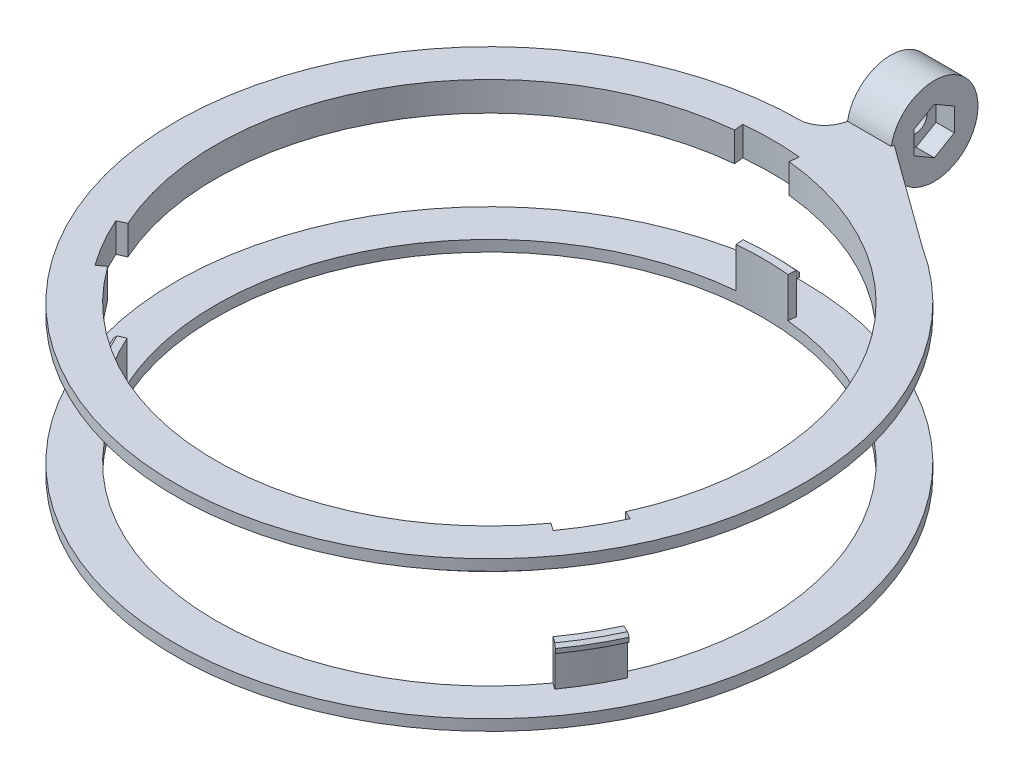
SolidWorks part; units mm, degrees
note: The reader was unsure of these and kept them because the rebuilt part matched: shared geometry of "Esboço120<3>", "Esboço120<4>", "Esboço122<12>", "Esboço123<3>".
ref_plane "Plano frontal" through (0, 0, 0) normal (0, 0, 1) x (1, 0, 0)
ref_plane "Plano superior" through (0, 0, 0) normal (0, 1, 0) x (1, 0, 0)
ref_plane "Plano direito" through (0, 0, 0) normal (1, 0, 0) x (0, 0, -1)
ref_plane "Plano24" through (10, 0, 0) normal (1, 0, 0) x (0, 0, -1)
sketch "Esboço120" plane through (10, 0, 0) normal (1, 0, 0) x (0, 0, -1)
  line L6 (-78.5, 184.9522) -> (-73.5, 176.2919)
  line L7 (-78.5, 176.2919) -> (-73.5, 184.9522)
  line L8 (-80.3301, 178.1221) -> (-71.6699, 183.1221)
  line L9 (-81, 180.6221) -> (-71, 180.6221)
  line L10 (-71.6699, 178.1221) -> (-80.3301, 183.1221)
  line L11 (-76, 185.6221) -> (-76, 175.6221)
  circle A0 centre (-76, 180.6221) radius 6
  circle A2 centre (-76, 180.6221) radius 1.5
  circle A4 centre (-76, 180.6221) radius 5
  dimension "D3" = 1
extrude "Ressalto-extrusão39" add sketch "Esboço120" along normal blind 6 separate body contours A0
extrude "Corte-Extrusão-Fina1" cut sketch "Esboço120<3>" along normal blind 0.4 thin contours L9 | L10 | L6 | L11 | L7 | L8
sketch "Esboço120<3>" plane through (10, 0, 0) normal (1, 0, 0) x (0, 0, -1) same geometry as "Esboço120"
extrude "Corte-extrusão49" cut sketch "Esboço120<4>" along normal up to next contours A2
sketch "Esboço120<4>" plane through (10, 0, 0) normal (1, 0, 0) x (0, 0, -1) same geometry as "Esboço120"
sketch "Esboço121" plane through (16, 0, 0) normal (1, 0, 0) x (0, 0, -1)
  line L1 (-76, 183.7975) -> (-78.75, 182.2098)
  line L2 (-78.75, 182.2098) -> (-78.75, 179.0343)
  line L3 (-78.75, 179.0343) -> (-76, 177.4466)
  line L4 (-76, 177.4466) -> (-73.25, 179.0343)
  line L5 (-73.25, 179.0343) -> (-73.25, 182.2098)
  line L6 (-73.25, 182.2098) -> (-76, 183.7975)
  circle A0 centre (-76, 180.6221) radius 2.75 construction
  dimension "D1" = 5.5
extrude "Corte-extrusão50" cut sketch "Esboço121" against normal blind 2.5 contours L1 L2 L3 L4 L5 L6
ref_plane "Plao25" through (0, 180.2338, 0) normal (0, 1, 0) x (1, 0, 0)
sketch "Esboço122" plane through (0, 180.2338, 0) normal (0, 1, 0) x (1, 0, 0)
  line L0 (10, -82) -> (10, -81.5)
  line L1 (10, -82) -> (7, -82) construction
  line L2 (7, -82) -> (7, -85) construction
  line L3 (10, -81.5) -> (16, -81.5)
  line L4 (10.8078, -90.6938) -> (10.9347, -89.4503)
  line L5 (7, -85) -> (7, -93) construction
  line L6 (3.311, -90.6819) -> (3.1881, -89.4379)
  line L7 (41.1629, -143.4643) -> (42.3017, -143.9798)
  line L8 (37.4042, -149.9507) -> (38.4177, -150.6824)
  line L9 (-23.474, -149.8538) -> (-24.4898, -150.5823)
  line L10 (-27.212, -143.3555) -> (-28.3524, -143.8673)
  circle A0 centre (7, -128) radius 43
  circle A1 centre (7, -128) radius 39.5
  circle A2 centre (7, -128) radius 40 construction
  circle A3 centre (7, -128) radius 42 construction
  circle A4 centre (7, -128) radius 37.5
  arc A5 (10.9347, -89.4503) -> (3.1881, -89.4379) centre (7, -128) ccw
  arc A6 (38.4177, -150.6824) -> (42.3017, -143.9798) centre (7, -128) ccw
  arc A7 (-28.3524, -143.8673) -> (-24.4898, -150.5823) centre (7, -128) ccw
  spline S0 degree 2 poles (10, -82) (9.3918, -84.3997) (7, -85) knots 0 0 0 1 1 1
  spline S1 degree 1 poles (16, -81.5) (30.0958, -91.729) knots 0 0 1 1
  point P3 (10, -82)
  point P25 (0, 0)
  point P26 (19.4375, -84.1454)
  point P35 (7, -128)
  point P36 (0, 0)
  point P37 (0, 0)
  point P38 (0, 0)
  dimension "D2" = 3
  dimension "D3" = 86
  dimension "D5" = 79
  dimension "D8" = 80
  dimension "D11" = 1.25
  dimension "D12" = 3
  dimension "D1" = 3
  dimension "D7" = 0.5
  dimension "D4" = 3.5
  dimension "D6" = 0.5
  dimension "D9" = 2
  dimension "D10" = 2
extrude "Ressalto-extrusão40" add sketch "Esboço122" along normal blind 1.5 contours S1 L3 L0 S0 A0 | A0 A1 | A1 A4
extrude "Ressalto-extrusão41" add sketch "Esboço122<12>" against normal blind 2.5 contours A1 A4
sketch "Esboço122<12>" plane through (0, 180.2338, 0) normal (0, 1, 0) x (1, 0, 0) same geometry as "Esboço122"
ref_plane "Plano25" through (0, 162.7338, 0) normal (0, -1, 0) x (-1, 0, 0)
sketch "Esboço123" plane through (0, 162.7338, 0) normal (0, -1, 0) x (-1, 0, 0)
  line L0 (-10.6087, -90.674) -> (-10.7154, -89.6295)
  line L1 (-3.5101, -90.6627) -> (-3.4068, -89.6178)
  line L2 (-10.6088, -90.6735) -> (-10.7154, -89.6295) construction
  line L3 (-3.5101, -90.6622) -> (-3.4068, -89.6178) construction
  line L4 (-10.8078, -90.6938) -> (-10.9347, -89.4503) construction
  line L5 (-3.311, -90.6819) -> (-3.1881, -89.4379) construction
  line L6 (27.1296, -143.5377) -> (28.0875, -143.9677)
  line L7 (23.5901, -149.691) -> (24.4434, -150.3029)
  line L8 (27.212, -143.3555) -> (28.3524, -143.8673) construction
  line L9 (23.474, -149.8538) -> (24.4898, -150.5823) construction
  line L10 (-37.5209, -149.7882) -> (-38.3722, -150.4029)
  line L11 (-41.08, -143.6463) -> (-42.0365, -144.0793)
  line L12 (-10.8078, -90.6938) -> (-10.9347, -89.4503) construction
  line L13 (-3.311, -90.6819) -> (-3.1881, -89.4379) construction
  line L14 (-37.4042, -149.9507) -> (-38.4177, -150.6824) construction
  line L15 (-41.1629, -143.4643) -> (-42.3017, -143.9798) construction
  arc A0 (24.4434, -150.3029) -> (28.0875, -143.9677) centre (-7, -128) ccw
  arc A1 (-3.4068, -89.6178) -> (-10.7154, -89.6295) centre (-7, -128) ccw
  arc A2 (24.4898, -150.5823) -> (28.3524, -143.8673) centre (-7, -128) ccw construction
  circle A3 centre (-7, -128) radius 43
  circle A4 centre (-7, -128) radius 43
  circle A5 centre (-7, -128) radius 37.5
  circle A6 centre (-7, -128) radius 37.5
  arc A7 (-3.1881, -89.4379) -> (-10.9347, -89.4503) centre (-7, -128) ccw construction
  arc A8 (-42.0365, -144.0793) -> (-38.3722, -150.4029) centre (-7, -128) ccw
  arc A9 (-42.3017, -143.9798) -> (-38.4177, -150.6824) centre (-7, -128) ccw construction
  arc A10 (-3.1881, -89.4379) -> (-10.9347, -89.4503) centre (-7, -128) ccw construction
  point P35 (-7, -128)
  dimension "D1" = 0.2
  dimension "D2" = 0
  dimension "D3" = 0
  dimension "D4" = 3
extrude "Ressalto-extrusão42" add sketch "Esboço123" along normal blind 1.5 separate body
extrude "Ressalto-extrusão43" add sketch "Esboço123<3>" against normal blind 5.5 contours L11 A8 L10 A6 | A6 L7 A0 L6 | A6 L1 A1 L0
sketch "Esboço123<3>" plane through (0, 162.7338, 0) normal (0, -1, 0) x (-1, 0, 0) same geometry as "Esboço123"
ref_plane "Plano26" through (0, 168.2338, 0) normal (0, 1, 0) x (1, 0, 0)
sketch "Esboço124" plane through (0, 168.2338, 0) normal (0, 1, 0) x (1, 0, 0)
  line L0 (38.3722, -150.4029) -> (38.6977, -150.6353)
  line L1 (42.0365, -144.0793) -> (42.4001, -144.2462)
  line L2 (10.7154, -89.6295) -> (10.7539, -89.2313)
  line L3 (3.4068, -89.6178) -> (3.3695, -89.2196)
  line L4 (-28.0875, -143.9677) -> (-28.4516, -144.1334)
  line L5 (-24.4434, -150.3029) -> (-24.7696, -150.5343)
  arc A0 (38.3722, -150.4029) -> (42.0365, -144.0793) centre (7, -128) ccw construction
  arc A1 (10.7154, -89.6295) -> (3.4068, -89.6178) centre (7, -128) ccw construction
  arc A2 (-28.0875, -143.9677) -> (-24.4434, -150.3029) centre (7, -128) ccw construction
  arc A3 (38.3722, -150.4029) -> (42.0365, -144.0793) centre (7, -128) ccw
  arc A4 (10.7154, -89.6295) -> (3.4068, -89.6178) centre (7, -128) ccw
  arc A5 (-28.0875, -143.9677) -> (-24.4434, -150.3029) centre (7, -128) ccw
  arc A6 (38.6977, -150.6353) -> (42.4001, -144.2462) centre (7, -128) ccw
  arc A7 (10.7539, -89.2313) -> (3.3695, -89.2196) centre (7, -128) ccw
  arc A8 (-28.4516, -144.1334) -> (-24.7696, -150.5343) centre (7, -128) ccw
  dimension "D1" = 0.4
extrude "Ressalto-extrusão44" add sketch "Esboço124" against normal blind 1
chamfer "Chanfro1" distance 0.4 angle 45 3 edges at (40.7006, 168.2338, 147.5287) (-26.7626, 168.2338, 147.4213) (7.062, 168.2338, 89.05)
